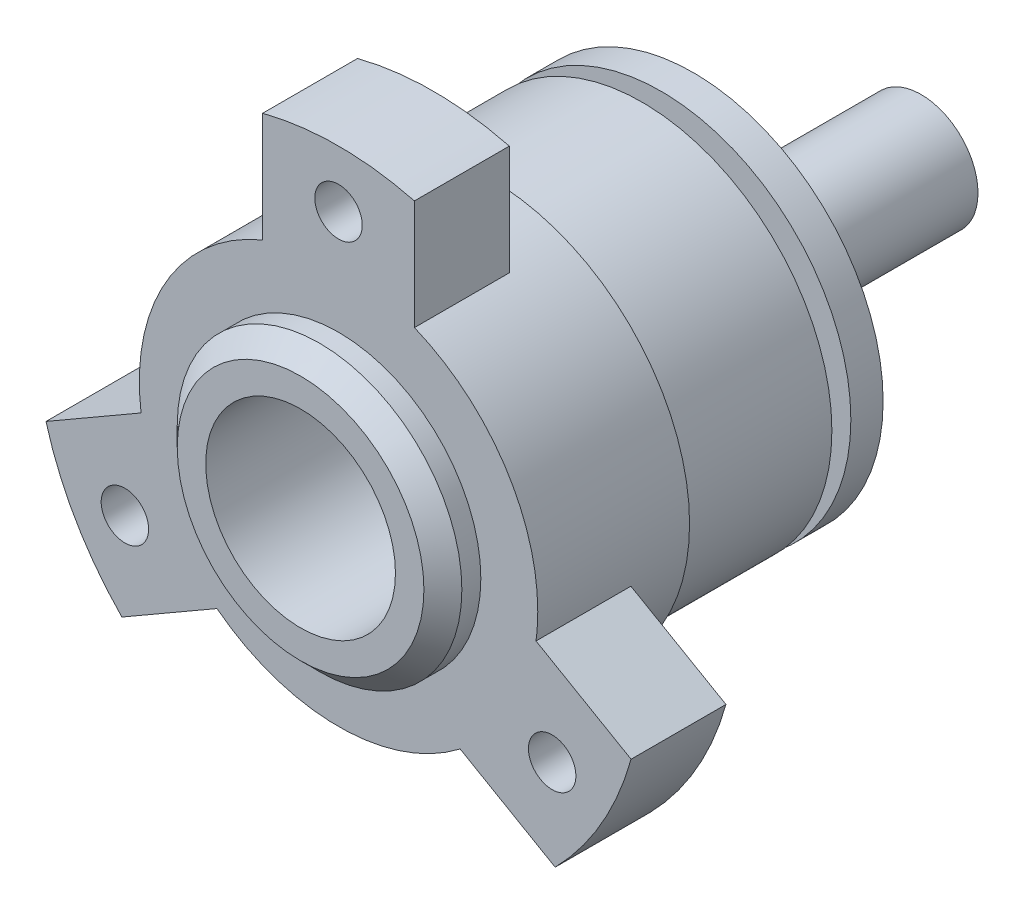
SolidWorks part; units mm, degrees
material "1060 合金"
ref_plane "前视基准面" through (0, 0, 0) normal (0, 0, 1) x (1, 0, 0)
ref_plane "上视基准面" through (0, 0, 0) normal (0, 1, 0) x (1, 0, 0)
ref_plane "右视基准面" through (0, 0, 0) normal (1, 0, 0) x (0, 0, -1)
sketch "草图1" plane through (0, 0, 0) normal (1, 0, 0) x (0, 0, -1)
  line L0 (0, 43.0226) -> (0, 0) construction
  line L1 (0, 0) -> (32.7, 0)
  line L2 (19, 10) -> (20.7, 10)
  line L4 (0, 0) -> (0, 7.5)
  line L5 (0, 7.5) -> (2, 7.5)
  line L7 (32.7, 0) -> (67.1157, 0) construction
  line L8 (2, 7.5) -> (2, 16)
  line L9 (2, 16) -> (7, 16)
  line L10 (7, 10.5) -> (7, 16)
  line L11 (7, 10.5) -> (10, 10.5)
  line L12 (20.7, 3) -> (32.7, 3)
  line L14 (10, 10.5) -> (10, 10)
  line L16 (32.7, 3) -> (32.7, 0)
  line L17 (10, 10) -> (18, 10)
  line L18 (20.7, 3) -> (20.7, 10)
  line L20 (18, 10) -> (18, 8.5)
  line L21 (18, 8.5) -> (19, 8.5)
  line L22 (19, 10) -> (19, 8.5)
  dimension "D1" = 2
  dimension "D2" = 7.5
  dimension "D3" = 16
  dimension "D4" = 5
  dimension "D5" = 3
  dimension "D6" = 8
  dimension "D7" = 3
  dimension "D8" = 1
  dimension "D9" = 1.5
  dimension "D10" = 1.7
  dimension "D11" = 0.5
  dimension "D12" = 12
  dimension "D13" = 10
revolve "旋转1" add sketch "草图1" angle 360 about L1
hole_wizard "M3 螺纹孔1" positions "草图3" profile "草图2" tap size "M3" standard "GB" end condition through all
sketch "草图3" plane through (0, 0, -2) normal (0, 0, 1) x (1, 0, 0)
  line L0 (0, 0) -> (0, 19.3219) construction
  circle A0 centre (0, 0) radius 13 construction
  point P0 (0, 13)
  point P23 (11.2583, -6.5)
  point P24 (-11.2583, -6.5)
  dimension "D1" = 26
  dimension "D2" = 3
sketch "草图2" plane through (0, 13, -2) normal (1, 0, 0) x (0, -1, 0)
  line L0 (0, 0) -> (0, 30.7)
  line L1 (0, 30.7) -> (1.25, 30.7)
  line L2 (1.25, 30.7) -> (1.25, 0)
  line L5 (1.25, 0) -> (0, 0)
  line L11 (0, -6.35) -> (0, 107.95) construction
  dimension "通孔螺纹孔钻头直径" = 2.5
  dimension "通孔螺纹孔钻头深度" = 30.7
cosmetic thread "孔螺蚊线1" parameters "D2"=3
cosmetic thread "孔螺蚊线2" parameters "D2"=3
cosmetic thread "孔螺蚊线3" parameters "D2"=3
sketch "草图4" plane through (0, 0, -2) normal (0, 0, 1) x (1, 0, 0)
  line L0 (0, 0) -> (0, 18.9172) construction
  line L1 (4, 15.4919) -> (4, 9.7082)
  line L2 (-4, 15.4919) -> (-4, 9.7082)
  line L3 (15.4164, -4.2819) -> (10.4076, -1.39)
  line L4 (11.4164, -11.2101) -> (6.4076, -8.3182)
  line L5 (-11.4164, -11.2101) -> (-6.4076, -8.3182)
  line L6 (-15.4164, -4.2819) -> (-10.4076, -1.39)
  circle A0 centre (0, 0) radius 16 construction
  arc A1 (4, 15.4919) -> (-4, 15.4919) centre (0, 0) ccw
  arc A2 (-4, 9.7082) -> (-10.4076, -1.39) centre (0, 0) ccw
  arc A4 (11.4164, -11.2101) -> (15.4164, -4.2819) centre (0, 0) ccw
  arc A5 (10.4076, -1.39) -> (4, 9.7082) centre (0, 0) ccw
  arc A6 (-15.4164, -4.2819) -> (-11.4164, -11.2101) centre (0, 0) ccw
  arc A7 (-6.4076, -8.3182) -> (6.4076, -8.3182) centre (0, 0) ccw
  circle A9 centre (0, 0) radius 10.5 construction
  dimension "D2" = 8
  dimension "D3" = 3
extrude "切除-拉伸4" cut sketch "草图4" against normal up to surface (5 mm away) flip side to cut up to face at (1.25, 13, -7)
chamfer "倒角1" distance 1 angle 45 1 edges at (7.5, 0, 0)
sketch "草图5" plane through (0, 0, 0) normal (0, 0, 1) x (1, 0, 0)
  circle A0 centre (0, 0) radius 5
  dimension "D1" = 10
extrude "减重孔" cut sketch "草图5" against normal blind 14
ref_plane "基准面1" through (3, 0, 0) normal (1, 0, 0) x (0, 0, -1)
sketch "草图9" plane through (3, 0, 0) normal (1, 0, 0) x (0, 0, -1)
  line L0 (0, 0) -> (40.9458, 0) construction
  line L3 (0, 6.5) -> (0, -6.5) construction
  line L4 (20.7, -10) -> (20.7, 10) construction
  circle A0 centre (23.7, 0) radius 1.5
  dimension "D2" = 3
  dimension "D1" = 3
extrude "切除-拉伸5" [suppressed] cut sketch "草图9" against normal blind 2
move or copy body "实体-移动/复制1" [suppressed] bodies to move or copy 105
